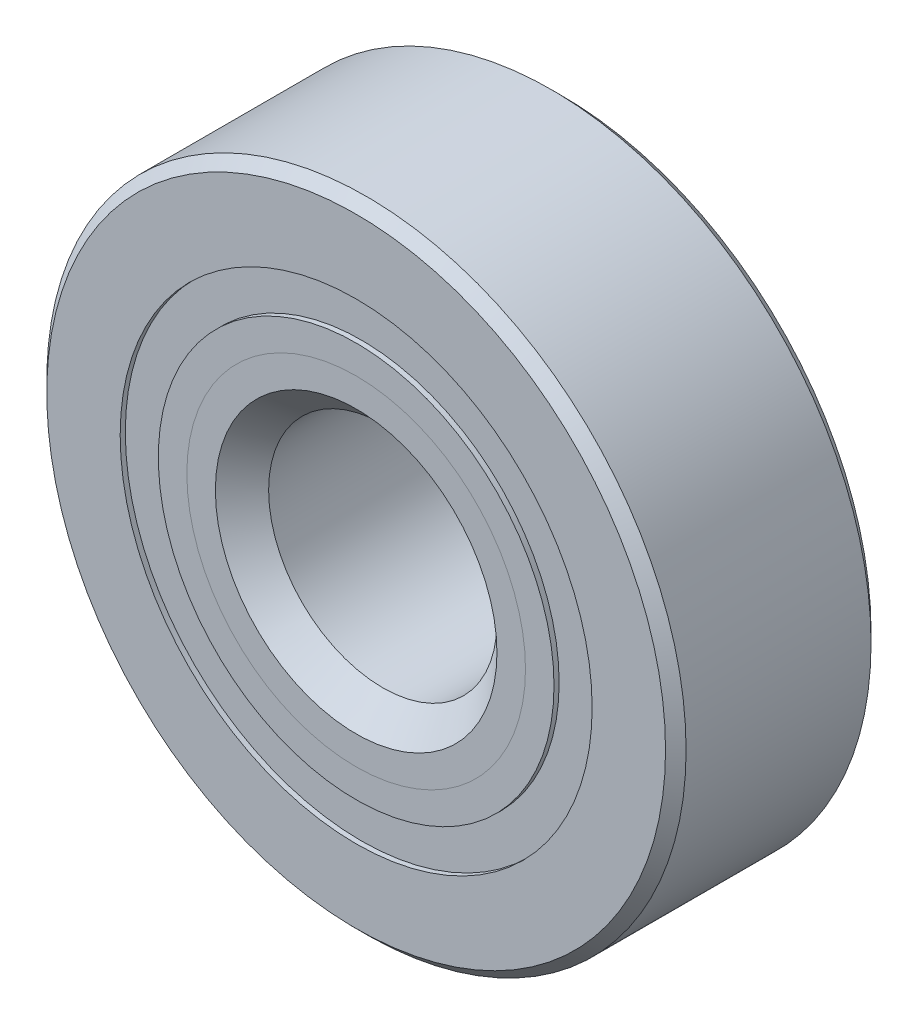
SolidWorks part; units mm, degrees
ref_plane "Front Plane" through (0, 0, 0) normal (0, 0, 1) x (1, 0, 0)
ref_plane "Top Plane" through (0, 0, 0) normal (0, 1, 0) x (1, 0, 0)
ref_plane "Right Plane" through (0, 0, 0) normal (1, 0, 0) x (0, 0, -1)
sketch "Sketch1" plane through (0, 0, 0) normal (1, 0, 0) x (0, 0, -1)
  line L0 (-3.5719, 0) -> (3.5719, 0) construction
  line L1 (0, 11.1125) -> (0, -11.1125) construction
  line L2 (3.2147, 11.1125) -> (-3.2147, 11.1125)
  line L3 (-3.2147, 11.1125) -> (-3.5719, 10.7553)
  line L4 (-3.5719, 10.7553) -> (-3.5719, 8.2035)
  line L5 (-3.5719, 8.2035) -> (-1.5875, 8.2035)
  line L6 (3.5719, 8.2035) -> (1.5875, 8.2035)
  line L7 (3.5719, 10.7553) -> (3.5719, 8.2035)
  line L8 (3.2147, 11.1125) -> (3.5719, 10.7553)
  line L9 (0, 11.1125) -> (0, 7.5406) construction
  line L10 (0, 7.5406) -> (0, 3.9688) construction
  arc A0 (-1.5875, 8.2035) -> (1.5875, 8.2035) centre (0, 7.5406) cw
  point P14 (0, 3.9688)
  dimension "Width" = 7.1437
  dimension "OD" = 22.225
  dimension "D1" = 45
  dimension "D2" = 0.3572
  dimension "D3" = 3.175
  dimension "D4" = 0.6629
revolve "Revolve1" add sketch "Sketch1" angle 360 about L0
sketch "Sketch2" plane through (0, 0, 0) normal (1, 0, 0) x (0, 0, -1)
  line L0 (-3.5719, 6.8777) -> (-1.5875, 6.8777)
  line L1 (-3.5719, 10.7553) -> (-3.5719, -10.7553) construction
  line L2 (-3.5719, 6.8777) -> (-3.5719, 5.8861)
  line L3 (-3.5719, 5.8861) -> (-2.5803, 4.8945)
  line L4 (-2.5803, 4.8945) -> (0, 4.8945)
  line L5 (0, 11.1125) -> (0, -11.1125) construction
  line L6 (0, 4.8945) -> (0, 5.8203)
  line L7 (0, 5.8203) -> (0, 3.9688) construction
  line L8 (-3.5719, 6.8777) -> (-3.5719, 4.8945) construction
  line L9 (-3.5719, 4.8945) -> (-2.5803, 4.8945) construction
  arc A0 (-1.5875, 6.8777) -> (0, 5.8203) centre (0, 7.5406) ccw
  arc A1 (1.5875, 8.2035) -> (-1.5875, 8.2035) centre (0, 7.5406) ccw construction
  circle A2 centre (0, 7.5406) radius 1.7204 construction
  dimension "D1" = 45
revolve "Revolve2" add sketch "Sketch2" angle 360 about L0
sketch "Sketch3" plane through (0, 0, 0) normal (1, 0, 0) x (0, 0, -1)
  line L0 (-3.5719, 5.8861) -> (-2.5803, 4.8945)
  line L1 (-2.5803, 4.8945) -> (0, 4.8945)
  line L2 (0, 4.8945) -> (0, 5.8203)
  line L3 (-3.5719, 5.8861) -> (-3.5719, 4.8945)
  line L4 (-3.5719, 6.8777) -> (-3.5719, 4.8945) construction
  line L5 (-3.5719, 4.8945) -> (-2.6461, 3.9688)
  line L6 (-2.6461, 3.9688) -> (3.2147, 3.9688)
  line L7 (3.2147, 11.1125) -> (3.2147, -11.1125) construction
  line L8 (3.2147, 3.9688) -> (3.5719, 4.3259)
  line L9 (3.5719, -10.7553) -> (3.5719, 10.7553) construction
  line L10 (3.5719, 4.3259) -> (3.5719, 6.8777)
  line L11 (3.5719, 6.8777) -> (1.5875, 6.8777)
  line L13 (3.2147, 11.1125) -> (3.5719, 10.7553) construction
  circle A0 centre (0, 7.5406) radius 1.7204 construction
  arc A1 (1.5875, 6.8777) -> (0, 5.8203) centre (0, 7.5406) cw
revolve "Revolve3" add sketch "Sketch3" angle 360 about L0
sketch "Sketch4" plane through (0, 0, 0) normal (1, 0, 0) x (0, 0, -1)
  line L0 (-1.7204, 7.5406) -> (1.7204, 7.5406)
  circle A1 centre (0, 7.5406) radius 1.7204 construction
  arc A2 (-1.7204, 7.5406) -> (1.7204, 7.5406) centre (0, 7.5406) cw
  arc A3 (1.5875, 8.2035) -> (-1.5875, 8.2035) centre (0, 7.5406) ccw construction
revolve "Revolve4" add sketch "Sketch4" angle 360 about L0
ref_axis "Axis1" through (0, 0, -3.5719) along (0, 0, 1)
pattern_circular "CirPattern1" count 8 every 45 about axis through (0, 0, -3.5719) along (0, 0, 1) of bodies 104
sketch "Sketch5" plane through (0, 0, 0) normal (1, 0, 0) x (0, 0, -1)
  line L0 (-3.5719, 8.2035) -> (-1.5875, 8.2035) construction
  line L1 (-3.3933, 8.2035) -> (-1.7204, 8.2035)
  line L2 (-3.3933, 8.2035) -> (-3.3933, 6.8777)
  line L3 (-3.3933, 6.8777) -> (-1.7204, 6.8777)
  line L4 (-1.7204, 8.2035) -> (-1.7204, 6.8777)
  line L5 (-3.5719, 6.8777) -> (-1.5875, 6.8777) construction
  line L6 (-3.2147, 11.1125) -> (-3.5719, 10.7553) construction
  line L7 (0, 11.1125) -> (0, 3.9688) construction
  line L8 (3.3933, 6.8777) -> (1.7204, 6.8777)
  line L9 (1.7204, 8.2035) -> (1.7204, 6.8777)
  line L10 (3.3933, 8.2035) -> (1.7204, 8.2035)
  line L11 (3.3933, 8.2035) -> (3.3933, 6.8777)
  circle A0 centre (0, 7.5406) radius 1.7204 construction
  point P10 (-3.3933, 10.9339)
revolve "Revolve5" add sketch "Sketch5" angle 360 about L0
equation "\"D2@Sketch1\" = \"Width@Sketch1\"*.05"
equation "\"D3@Sketch1\" = \"Width@Sketch1\"/2.25"
equation "\"D4@Sketch1\" = (((\"OD@Sketch1\"-\"Width@Sketch1\")/2)/3.25)/3.5"
equation "\"D2@CirPattern1\" = 360/\"Balls@CirPattern1\""
